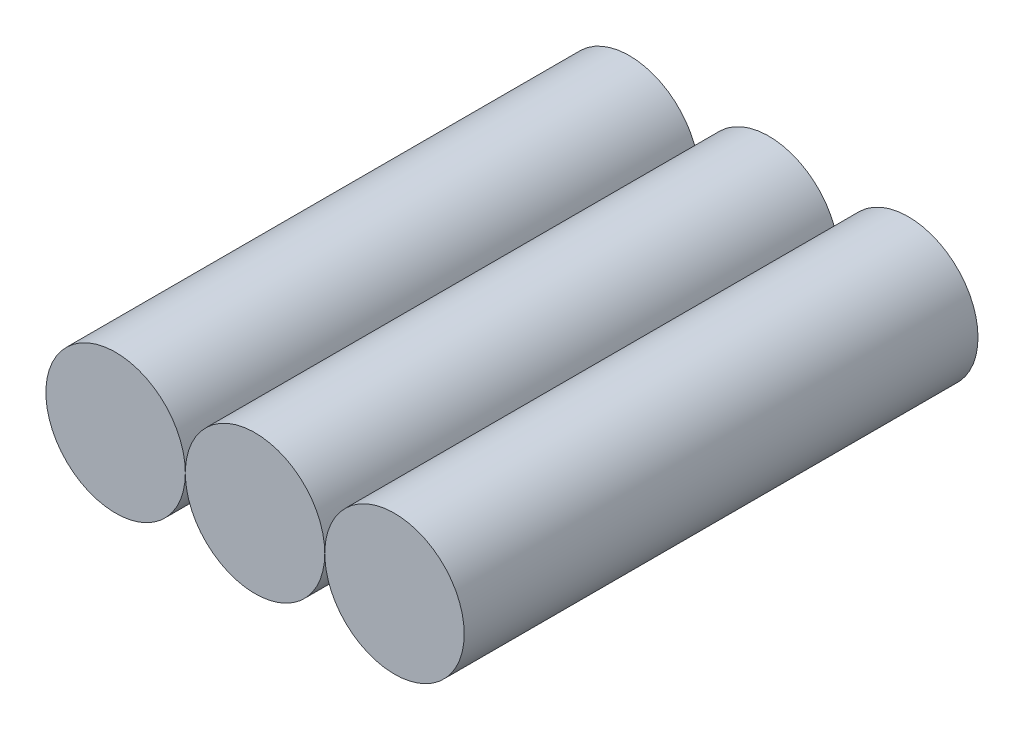
SolidWorks part; units mm, degrees
ref_plane "Front Plane" through (0, 0, 0) normal (0, 0, 1) x (1, 0, 0)
ref_plane "Top Plane" through (0, 0, 0) normal (0, 1, 0) x (1, 0, 0)
ref_plane "Right Plane" through (0, 0, 0) normal (1, 0, 0) x (0, 0, -1)
sketch "Sketch1" plane through (0, 0, 0) normal (0, 0, 1) x (1, 0, 0)
  line L0 (0, 0) -> (28.1527, 0) construction
  circle A0 centre (0, 0) radius 9.5
  circle A1 centre (19, 0) radius 9.5
  circle A2 centre (-19, 0) radius 9.5
  dimension "D1" = 19
extrude "Boss-Extrude1" add sketch "Sketch1" along normal blind 35 and the other way blind 35 contours A2 L0 | A0 L0 | A1 L0 | L0 A1 | L0 A0 | L0 A2 region at (0, -9.2313, 0) region at (-19, 0, 0) region at (19, 9.2313, 0)
